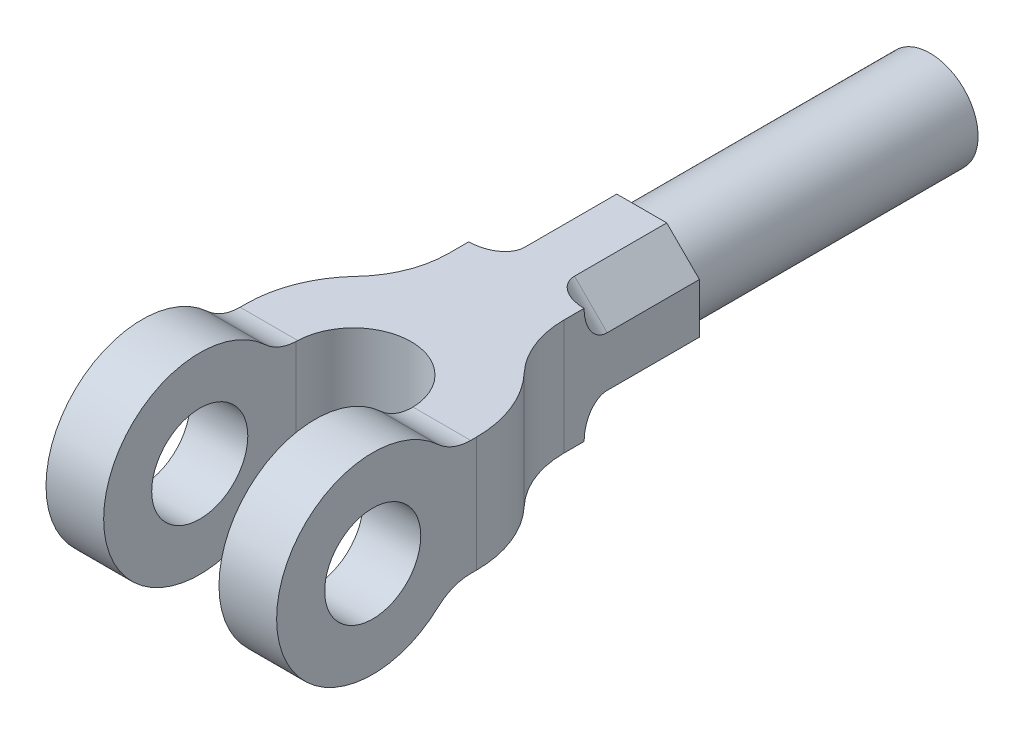
SolidWorks part; units mm, degrees
ref_plane "Front Plane" through (0, 0, 0) normal (0, 0, 1) x (1, 0, 0)
ref_plane "Top Plane" through (0, 0, 0) normal (0, 1, 0) x (1, 0, 0)
ref_plane "Right Plane" through (0, 0, 0) normal (1, 0, 0) x (0, 0, -1)
sketch "Sketch1" plane through (0, 0, 0) normal (0, 1, 0) x (1, 0, 0)
  line L1 (-600, 1250) -> (600, 1250)
  line L2 (-600, 1250) -> (-600, -1250)
  line L3 (-600, -1250) -> (600, -1250)
  line L4 (600, 1250) -> (600, -1250)
  line L5 (-600, 1250) -> (600, -1250) construction
  line L6 (-600, -1250) -> (600, 1250) construction
  point P0 (0, 0)
  dimension "D1" = 1200
  dimension "D2" = 2500
extrude "Boss-Extrude1" add sketch "Sketch1" along normal blind 1000
sketch "Sketch2" plane through (0, 1000, 0) normal (0, 1, 0) x (1, 0, 0)
  line L0 (0, 1548.1361) -> (0, -1394.2278) construction
  line L1 (600, 1250) -> (-600, 1250) construction
  line L2 (-300, 1250) -> (-300, 544.9834)
  line L3 (300, 1250) -> (300, 544.9834)
  line L4 (-300, -250) -> (-300, -1250)
  line L5 (300, -250) -> (300, -1250)
  line L8 (600, -1250) -> (600, 1250)
  line L9 (600, 1250) -> (-600, 1250)
  line L10 (-600, 1250) -> (-600, -1250)
  line L11 (-600, -1250) -> (600, -1250)
  line L12 (600, -1250) -> (600, 1250)
  line L13 (600, 1250) -> (-600, 1250)
  line L14 (-600, 1250) -> (-600, -1250)
  line L15 (-600, -1250) -> (600, -1250)
  arc A0 (300, -250) -> (-300, -250) centre (0, -250) ccw
  arc A1 (-436.3636, 201.8092) -> (436.3636, 201.8092) centre (0, -210) ccw
  arc A2 (300, 544.9834) -> (436.3636, 201.8092) centre (800, 544.9834) ccw
  arc A3 (-300, 544.9834) -> (-436.3636, 201.8092) centre (-800, 544.9834) cw
  point P17 (300, 309.6152)
  point P21 (-300, 309.6152)
  line M12 (600, 1250) -> (-600, 1250)
  line M13 (-600, 1250) -> (-600, -1250)
  line M14 (-600, -1250) -> (600, -1250)
  dimension "D1" = 600
  dimension "D2" = 1200
  dimension "D7" = 500
  dimension "D3" = 40
  dimension "D4" = 1500
  dimension "D5" = 300
  dimension "D6" = 0
extrude "Cut-Extrude1" cut sketch "Sketch2" against normal blind 1000 contours A3 L2 A1 M12 M13 | L3 A2 A1 L12 M12 | A0 L0 A1 L5 | L0 A0 L4 A1 | L0 A1 L4 M14 | A1 L0 L15 L5 region at (140.4851, 1000, 396.6259) region at (-140.4851, 1000, 396.6259) region at (461.7481, 1000, -705.027) region at (-461.7481, 1000, -705.027) region at (154.2478, 1000, 1016.3805) region at (-154.2478, 1000, 1016.3805)
sketch "Sketch3" plane through (600, 0, 0) normal (1, 0, 0) x (0, 0, -1)
  line L0 (-1250, 1000) -> (-1250, 0) construction
  line L1 (-1250, 0) -> (-210, 0) construction
  line L2 (-750, 500) -> (1250, 500) construction
  line L3 (1250, 0) -> (1250, 1000) construction
  line L4 (-210, 0) -> (201.8092, 0) construction
  line L5 (-240.098, 800) -> (1250, 800)
  line L7 (-240.098, 200) -> (1250, 200)
  line L8 (1250, 800) -> (1250, 200)
  line L9 (201.8092, 0) -> (544.9834, 0) construction
  line L10 (1250, 0) -> (544.9834, 0) construction
  line L11 (1250, 1000) -> (544.9834, 1000) construction
  line L12 (544.9834, 1000) -> (201.8092, 1000) construction
  line L13 (201.8092, 1000) -> (-210, 1000) construction
  line L14 (-1250, 1000) -> (-210, 1000) construction
  line L15 (-1250, 1000) -> (-1250, 0)
  line L16 (-1250, 0) -> (-210, 0)
  line L17 (-210, 0) -> (201.8092, 0)
  line L18 (201.8092, 0) -> (544.9834, 0)
  line L19 (1250, 0) -> (544.9834, 0)
  line L20 (1250, 0) -> (1250, 1000)
  line L21 (1250, 1000) -> (544.9834, 1000)
  line L22 (544.9834, 1000) -> (201.8092, 1000)
  line L23 (201.8092, 1000) -> (-210, 1000)
  line L24 (-1250, 1000) -> (-210, 1000)
  arc A0 (-410.0654, 866.6667) -> (-410.0654, 133.3333) centre (-750, 500) ccw
  circle A1 centre (-750, 500) radius 250
  arc A2 (-410.0654, 133.3333) -> (-240.098, 200) centre (-240.098, -50) cw
  arc A3 (-410.0654, 866.6667) -> (-240.098, 800) centre (-240.098, 1050) ccw
  line M19 (-1250, 0) -> (-210, 0)
  line M20 (-210, 0) -> (-210, 1000)
  line M21 (-210, 1000) -> (-1250, 1000)
  line M22 (-1250, 1000) -> (-1250, 0)
  dimension "D1" = 500
  dimension "D3" = 250
  dimension "D2" = 600
extrude "Cut-Extrude4" cut sketch "Sketch3" against normal blind 1315 contours A0 L24 M22 | A0 A3 L5 M20 M21 | L22 L23 L5 L20 L21 M20 | L19 L20 L7 L17 L18 M20 | A2 A0 L16 L7 M20 | A0 L15 M19 | A1 region at (600, 922.7719, 357.085) region at (600, 900, -520) region at (600, 77.2281, 357.085) region at (600, 100, -520) region at (600, 888.316, 1138.316) region at (600, 111.684, 1138.316) region at (600, 500, 750)
sketch "Sketch4" plane through (0, 0, -1250) normal (0, 0, -1) x (-1, 0, 0)
  line L0 (300, 800) -> (300, 630)
  line L1 (300, 200) -> (300, 800) construction
  line L2 (300, 630) -> (130, 800)
  line L3 (300, 800) -> (-300, 800) construction
  line L4 (130, 800) -> (300, 800)
  line L5 (300, 370) -> (300, 200)
  line L6 (300, 200) -> (130, 200)
  line L7 (130, 200) -> (300, 370)
  line L8 (-130, 200) -> (-300, 200)
  line L9 (-300, 200) -> (-300, 370)
  line L10 (-300, 370) -> (-130, 200)
  line L11 (-300, 630) -> (-300, 800)
  line L12 (-300, 800) -> (-130, 800)
  line L13 (-130, 800) -> (-300, 630)
  circle A0 centre (0, 500) radius 250
  dimension "D1" = 500
  dimension "D2" = 170
  dimension "D3" = 170
  dimension "D4" = 4
extrude "Cut-Extrude9" cut sketch "Sketch4" against normal blind 600 contours L13 L11 L5 | L2 L6 L11 | L7 L10 L6 | L10 L5 region at (-243.3333, 743.3333, -1250) region at (-243.3333, 256.6667, -1250) region at (243.3333, 256.6667, -1250) region at (243.3333, 743.3333, -1250)
extrude "Boss-Extrude2" add sketch "Sketch4<3>" along normal blind 1500 contours A0 region at (0, 500, -1250)
sketch "Sketch4<3>" plane through (0, 0, -1250) normal (0, 0, -1) x (-1, 0, 0) same geometry as "Sketch4"
fillet "Fillet1" radius 120 1 edges at (-215, 715, -650) type face fillet first side face at (-215, 715, -950) second side face at (-243.3333, 743.3333, -650)
fillet "Fillet2" radius 120 1 edges at (-215, 285, -650) type face fillet first side face at (-215, 285, -950) second side face at (-243.3333, 256.6667, -650)
fillet "Fillet3" radius 120 1 edges at (215, 715, -650) type face fillet first side face at (215, 715, -950) second side face at (243.3333, 743.3333, -650)
fillet "Fillet4" radius 120 1 edges at (215, 285, -650) type face fillet first side face at (215, 285, -950) second side face at (243.3333, 256.6667, -650)
